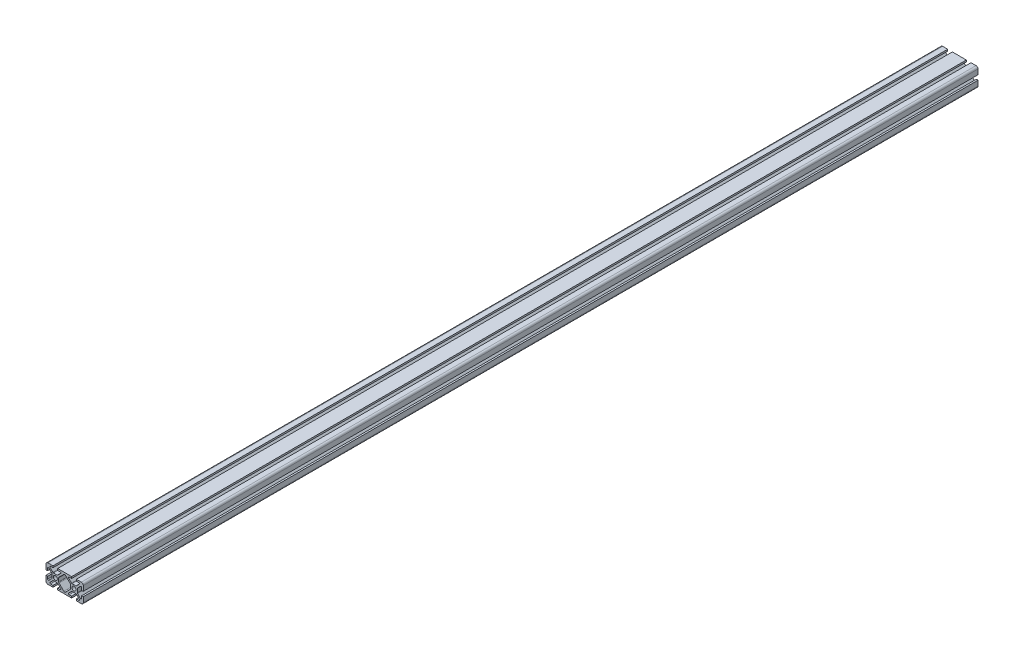
SolidWorks part; units mm, degrees
material "6061 Alloy"
ref_plane "Front Plane" through (0, 0, 0) normal (0, 0, 1) x (1, 0, 0)
ref_plane "Top Plane" through (0, 0, 0) normal (0, 1, 0) x (1, 0, 0)
ref_plane "Right Plane" through (0, 0, 0) normal (1, 0, 0) x (0, 0, -1)
sketch "Sketch1" plane through (0, 0, 0) normal (0, 0, 1) x (1, 0, 0)
  line L0 (10, 10) -> (10, -10) construction
  line L1 (-20, 0) -> (20, 0) construction
  line L2 (12.5, -10) -> (20, -10)
  line L3 (20, -10) -> (20, -2.5)
  line L4 (12.5, -10) -> (12.5, -8.2134)
  line L5 (12.5, -8.2134) -> (16.95, -8.2134)
  line L6 (16.95, -8.2134) -> (12.3366, -3.6)
  line L7 (10, 0) -> (20, -10) construction
  line L8 (20, -2.5) -> (18.2134, -2.5)
  line L9 (18.2134, -2.5) -> (18.2134, -6.95)
  line L10 (18.2134, -6.95) -> (13.6, -2.3366)
  line L11 (15.9067, -4.6433) -> (14.6433, -5.9067) construction
  line L12 (0, 10) -> (0, -10) construction
  line L13 (0, -10) -> (-20, -10) construction
  line L14 (-10, 10) -> (10, 10) construction
  line L15 (20, 2.5) -> (20, -2.5) construction
  circle A0 centre (10, 0) radius 2.15
  arc A1 (15.5015, -8.2134) -> (15.9257, -7.1891) centre (15.5015, -7.6134) ccw construction
  point P8 (10, -3.6)
  point P16 (15.275, -5.275)
  point P30 (20, 0)
  dimension "Center Hole Diameter" = 4.3
  dimension "D3" = 0.6
  dimension "Rail Width" = 20
  dimension "T-Slot Width" = 5
  dimension "Slot Depth" = 6.4
  dimension "Rail Height" = 40
  dimension "Inner Slot Width" = 13.9
  dimension "Hole Spacing" = 20
sketch "Sketch2" plane through (0, 0, 0) normal (1, 0, 0) x (0, 0, -1)
  line L0 (-480, -10) -> (480, -10) construction
  line L1 (-440, 0) -> (440, 0) construction
  point P6 (-440, 0)
  point P8 (440, 0)
  dimension "Length" = 960
  dimension "D1" = 40
sketch "Sketch3" plane through (0, 0, 0) normal (0, 0, 1) x (1, 0, 0)
  line L0 (12.5, -10) -> (17.9, -10)
  line L1 (12.5, -10) -> (20, -10) construction
  line L2 (12.5, -10) -> (12.5, -8.2134) construction
  line L3 (12.5, -8.2134) -> (16.95, -8.2134) construction
  line L4 (12.5, -8.2134) -> (12.5, -10)
  line L5 (12.5, -8.2134) -> (16.95, -8.2134)
  line L6 (10, -3.6) -> (12.3366, -3.6)
  line L7 (16.95, -8.2134) -> (12.3366, -3.6) construction
  line L8 (12.3366, -3.6) -> (16.95, -8.2134)
  line L9 (20, -10) -> (20, -2.5) construction
  line L10 (18.2134, -6.95) -> (13.6, -2.3366) construction
  line L11 (18.2134, -2.5) -> (18.2134, -6.95) construction
  line L12 (18.2134, -6.95) -> (18.2134, -2.5)
  line L13 (20, -2.5) -> (18.2134, -2.5) construction
  line L14 (18.2134, -2.5) -> (20, -2.5)
  line L15 (20, -2.5) -> (20, -7.9)
  line L16 (18.2134, -6.95) -> (13.6, -2.3366)
  line L17 (13.6, 0) -> (13.6, -2.3366)
  line L18 (-20, 0) -> (20, 0) construction
  line L19 (10, -3.6) -> (10, -2.15)
  line L20 (10, 10) -> (10, -10) construction
  line L21 (13.6, 0) -> (12.15, 0)
  arc A5 (17.9, -10) -> (20, -7.9) centre (17.9, -7.9) ccw
  circle A10 centre (10, 0) radius 2.15 construction
  arc A11 (10, -2.15) -> (12.15, 0) centre (10, 0) ccw
  dimension "D1" = 2.1
extrude "Boss-Extrude1" add sketch "Sketch3" along normal mid plane 960
sketch "Sketch4" plane through (0, 0, 0) normal (0, 0, 1) x (1, 0, 0)
  line L0 (10, -3.6) -> (7.6634, -3.6)
  line L4 (7.6634, -3.6) -> (3.05, -8.2134)
  line L5 (3.05, -8.2134) -> (7.5, -8.2134)
  line L6 (7.5, -8.2134) -> (7.5, -10)
  line L18 (7.5, -10) -> (0, -10)
  line L19 (12.5, -10) -> (12.5, -8.2134) construction
  line L20 (12.5, -8.2134) -> (16.95, -8.2134) construction
  line L21 (10, -3.6) -> (12.3366, -3.6) construction
  line L22 (16.95, -8.2134) -> (12.3366, -3.6) construction
  line L23 (0, -8.7366) -> (6.4, -2.3366)
  line L24 (0, 10) -> (0, -10) construction
  line L25 (6.4, -2.3366) -> (6.4, 0)
  line L26 (-20, 0) -> (20, 0) construction
  line L27 (6.4, 0) -> (7.85, 0)
  line L28 (13.6, 0) -> (12.15, 0) construction
  line L29 (0, -8.7366) -> (0, -10)
  line L30 (10, -2.15) -> (10, -3.6)
  circle A4 centre (10, 0) radius 2.15 construction
  arc A5 (7.85, 0) -> (10, -2.15) centre (10, 0) ccw
extrude "Boss-Extrude2" add sketch "Sketch4" along normal mid plane 960
mirror "Mirror1" about plane through (0, 0, 0) normal (1, 0, 0) of bodies 137 134
mirror "Mirror2" about plane through (0, 0, 0) normal (0, 1, 0) of bodies 135
fillet "Fillet1" radius 0.75 24 edges at (-7.6634, -3.6, 0) (-12.3366, -3.6, 0) (12.3366, -3.6, 0) (7.6634, -3.6, 0) (-3.05, -8.2134, 0) (-18.2134, -6.95, 0) (-16.95, -8.2134, 0) (-13.6, -2.3366, 0) (-18.2134, 6.95, 0) (-16.95, 8.2134, 0) (-12.3366, 3.6, 0) (-7.6634, 3.6, 0) (-13.6, 2.3366, 0) (-3.05, 8.2134, 0) (3.05, 8.2134, 0) (13.6, -2.3366, 0) (13.6, 2.3366, 0) (7.6634, 3.6, 0) (12.3366, 3.6, 0) (18.2134, 6.95, 0) (16.95, 8.2134, 0) (18.2134, -6.95, 0) (16.95, -8.2134, 0) (3.05, -8.2134, 0)
fillet "Fillet2" radius 1.25 6 edges at (0, -8.7366, 0) (-6.4, -2.3366, 0) (-6.4, 2.3366, 0) (6.4, -2.3366, 0) (6.4, 2.3366, 0) (0, 8.7366, 0)
equation "\"D1@Sketch3\" = \"D3@Sketch1\" * 3.5"
equation "\"D1@Boss-Extrude1\" = \"Length@Sketch2\""
equation "\"D1@Boss-Extrude2\" = \"Length@Sketch2\""
equation "\"D1@Sketch2\"=\"Rail Height@Sketch1\""
